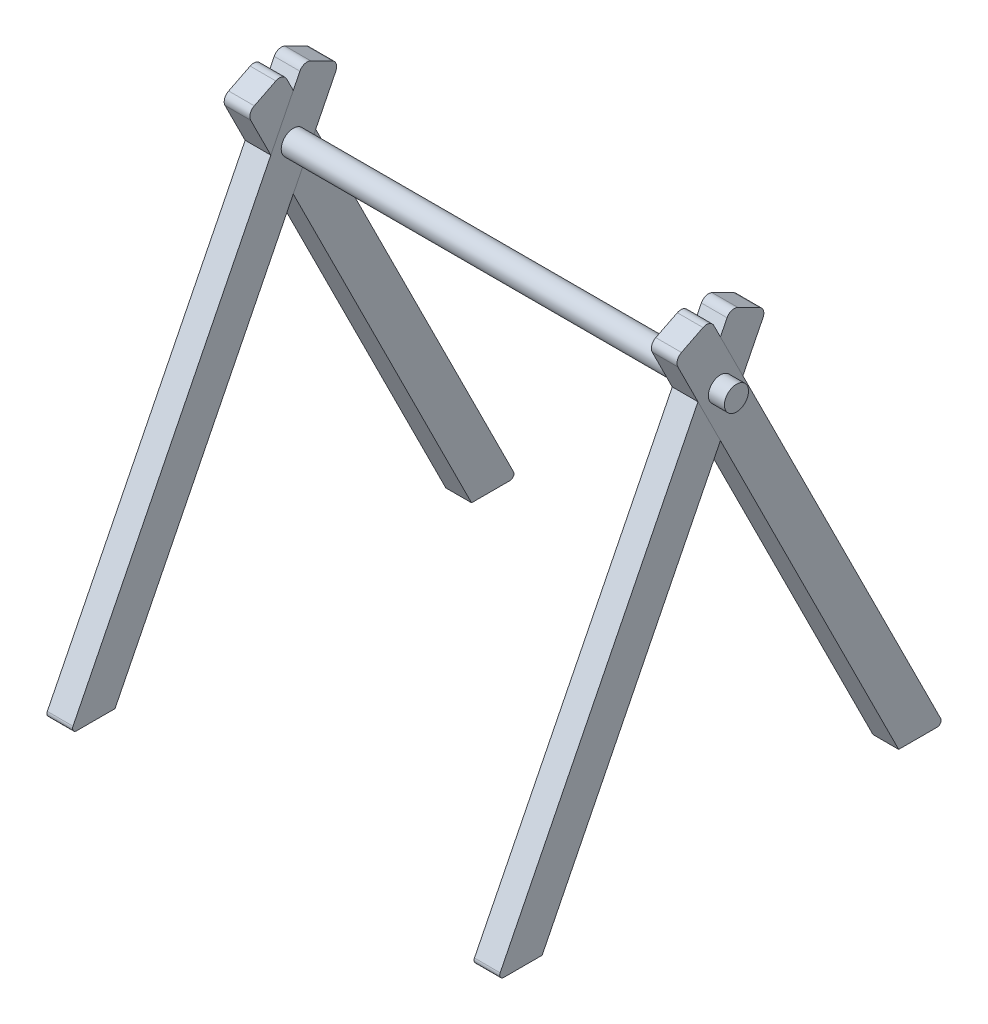
SolidWorks part; units mm, degrees
material "Pine"
ref_plane "Front Plane" through (0, 0, 0) normal (0, 0, 1) x (1, 0, 0)
ref_plane "Top Plane" through (0, 0, 0) normal (0, 1, 0) x (1, 0, 0)
ref_plane "Right Plane" through (0, 0, 0) normal (1, 0, 0) x (0, 0, -1)
sketch "Sketch1" plane through (0, 0, 0) normal (1, 0, 0) x (0, 0, -1)
  line L0 (-250, 0) -> (250, 0)
  line L1 (250, 0) -> (0, 500)
  line L2 (0, 500) -> (-250, 0)
  dimension "D1" = 500
  dimension "D2" = 500
sketch "Sketch3" plane through (0, 0, 0) normal (1, 0, 0) x (0, 0, -1)
  line L0 (-250, 0) -> (250, 0) construction
  line L1 (-402.0212, 0) -> (465.3533, 0) construction
  line L2 (12.738, 581.3777) -> (57.4593, 559.017)
  line L3 (-12.738, 581.3777) -> (-57.4593, 559.017)
  line L4 (-277.9508, 0) -> (-222.0492, 0)
  line L5 (222.0492, 0) -> (277.9508, 0)
  line L8 (-22.3607, 511.1803) -> (-272.3607, 11.1803)
  line L9 (12.738, 581.3777) -> (-277.9508, 0)
  line L10 (22.3607, 488.8197) -> (-227.6393, -11.1803)
  line L11 (57.4593, 559.017) -> (-222.0492, 0)
  line L13 (272.3607, 11.1803) -> (22.3607, 511.1803)
  line L14 (277.9508, 0) -> (-12.738, 581.3777)
  line L15 (227.6393, -11.1803) -> (-22.3607, 488.8197)
  line L16 (222.0492, 0) -> (-57.4593, 559.017)
  circle A0 centre (0, 500) radius 15
  dimension "D5" = 30
  dimension "D6" = 650
  dimension "D1" = 25
  dimension "D2" = 25
  dimension "D3" = 25
  dimension "D4" = 25
sketch "Sketch4" plane through (0, 0, 0) normal (1, 0, 0) x (0, 0, -1)
  line L0 (-277.9508, 0) -> (-222.0492, 0) construction
  line L1 (57.4593, 559.017) -> (-222.0492, 0) construction
  line L2 (12.738, 581.3777) -> (57.4593, 559.017) construction
  line L3 (12.738, 581.3777) -> (-277.9508, 0) construction
  line L4 (-277.9508, 0) -> (-222.0492, 0)
  line L5 (57.4593, 559.017) -> (-222.0492, 0)
  line L6 (12.738, 581.3777) -> (57.4593, 559.017)
  line L7 (12.738, 581.3777) -> (-277.9508, 0)
extrude "Boss-Extrude1" add sketch "Sketch4" along normal blind 32
sketch "Sketch5" plane through (0, 0, 0) normal (1, 0, 0) x (0, 0, -1)
  line L0 (-12.738, 581.3777) -> (-57.4593, 559.017) construction
  line L1 (222.0492, 0) -> (-57.4593, 559.017) construction
  line L2 (277.9508, 0) -> (-12.738, 581.3777) construction
  line L3 (222.0492, 0) -> (277.9508, 0) construction
  line L4 (222.0492, 0) -> (277.9508, 0)
  line L5 (-12.738, 581.3777) -> (-57.4593, 559.017)
  line L6 (277.9508, 0) -> (-12.738, 581.3777)
  line L7 (222.0492, 0) -> (-57.4593, 559.017)
extrude "Boss-Extrude2" add sketch "Sketch5" along normal blind 32 separate body
sketch "Sketch6" plane through (0, 0, 0) normal (-1, 0, 0) x (0, 0, 1)
  line L4 (12.738, 581.3777) -> (-277.9508, 0)
  line L5 (-277.9508, 0) -> (-222.0492, 0)
  line L6 (-222.0492, 0) -> (57.4593, 559.017)
  line L7 (57.4593, 559.017) -> (12.738, 581.3777)
  line L8 (12.738, 581.3777) -> (-277.9508, 0)
  line L9 (-277.9508, 0) -> (-222.0492, 0)
  line L10 (-222.0492, 0) -> (57.4593, 559.017)
  line L11 (57.4593, 559.017) -> (12.738, 581.3777)
  dimension "D1" = 0
extrude "Cut-Extrude1" cut sketch "Sketch6" against normal blind 16
sketch "Sketch7" plane through (32, 0, 0) normal (1, 0, 0) x (0, 0, -1)
  line L4 (12.738, 581.3777) -> (-277.9508, 0)
  line L5 (-277.9508, 0) -> (-222.0492, 0)
  line L6 (-222.0492, 0) -> (57.4593, 559.017)
  line L7 (57.4593, 559.017) -> (12.738, 581.3777)
  line L8 (12.738, 581.3777) -> (-277.9508, 0)
  line L9 (-277.9508, 0) -> (-222.0492, 0)
  line L10 (-222.0492, 0) -> (57.4593, 559.017)
  line L11 (57.4593, 559.017) -> (12.738, 581.3777)
  dimension "D1" = 0
extrude "Cut-Extrude2" cut sketch "Sketch7" against normal blind 16
sketch "Sketch8" plane through (32, 0, 0) normal (1, 0, 0) x (0, 0, -1)
  circle A0 centre (0, 500) radius 15 construction
  circle A1 centre (0, 500) radius 15
extrude "Cut-Extrude3" cut sketch "Sketch8" against normal through all
sketch "Sketch9" plane through (32, 0, 0) normal (1, 0, 0) x (0, 0, -1)
  circle A0 centre (0, 500) radius 3.25
  dimension "D1" = 6.5
extrude "Cut-Extrude4" cut sketch "Sketch9" against normal through all
fillet "Fillet1" radius 10 2 edges at (16, 559.017, 57.4593) (16, 581.3777, 12.738)
fillet "Fillet2" radius 10 2 edges at (16, 581.3777, -12.738) (16, 559.017, -57.4593)
fillet "Fillet3" radius 5 1 edges at (16, 0, 277.9508)
fillet "Fillet4" radius 5 1 edges at (16, 0, -277.9508)
ref_plane "Plane1" through (282, 0, 0) normal (1, 0, 0) x (0, 0, -1)
mirror "Mirror1" about plane through (282, 0, 0) normal (1, 0, 0) of bodies 106 107
sketch "Sketch10" plane through (16, 0, 0) normal (1, 0, 0) x (0, 0, -1)
  circle A0 centre (0, 500) radius 15 construction
  circle A1 centre (0, 500) radius 15
extrude "Boss-Extrude4" add sketch "Sketch10" along normal up to surface (532 mm away) separate body up to face at (548, 500, -3.25)
hole_wizard "M6 Tapped Hole1" positions "Sketch12" profile "Sketch14" tap size "M6" standard "ISO"
sketch "Sketch12" plane through (16, 0, 0) normal (-1, 0, 0) x (0, 0, 1)
  point P0 (0, 500)
sketch "Sketch14" plane through (16, 500, 0) normal (0, 1, 0) x (0, 0, 1)
  line L0 (0, 0) -> (0, 26.5022)
  line L1 (0, 26.5022) -> (2.5, 25)
  line L2 (2.5, 25) -> (2.5, 0)
  line L5 (2.5, 0) -> (0, 0)
  line L10 (0, 26.5022) -> (-2.5, 25) construction
  line L11 (0, -6.35) -> (0, 107.95) construction
  dimension "Tap Drill Dia." = 5
  dimension "Tap Drill Depth" = 25
  dimension "Drill Angle" = 118
cosmetic thread "Hole Thread1" parameters "D1"=22, "D2"=6
hole_wizard "M6 Tapped Hole2" positions "Sketch15" profile "Sketch16" tap size "M6" standard "ISO"
sketch "Sketch15" plane through (548, 0, 0) normal (1, 0, 0) x (0, 0, -1)
  point P0 (0, 500)
sketch "Sketch16" plane through (548, 500, 0) normal (0, 1, 0) x (0, 0, -1)
  line L0 (0, 0) -> (0, 26.5022)
  line L1 (0, 26.5022) -> (2.5, 25)
  line L2 (2.5, 25) -> (2.5, 0)
  line L5 (2.5, 0) -> (0, 0)
  line L10 (0, 26.5022) -> (-2.5, 25) construction
  line L11 (0, -6.35) -> (0, 107.95) construction
  dimension "Tap Drill Dia." = 5
  dimension "Tap Drill Depth" = 25
  dimension "Drill Angle" = 118
cosmetic thread "Hole Thread2" parameters "D1"=22, "D2"=6
sketch "Sketch17" plane through (16, 0, 0) normal (-1, 0, 0) x (0, 0, 1)
  circle A0 centre (0, 500) radius 3
  dimension "D1" = 6
extrude "Boss-Extrude5" add sketch "Sketch17" along normal blind 22 and the other way blind 20 separate body
mirror "Mirror3" about plane through (282, 0, 0) normal (1, 0, 0) of bodies 113
sketch "Sketch18" plane through (0, 0, 0) normal (-1, 0, 0) x (0, 0, 1)
  circle A1 centre (0, 500) radius 15 construction
  circle A2 centre (0, 500) radius 15
extrude "Boss-Extrude6" add sketch "Sketch18" along normal blind 20 separate body
sketch "Sketch19" plane through (0, 0, 0) normal (-1, 0, 0) x (0, 0, 1)
  circle A0 centre (0, 500) radius 3
  dimension "D1" = 6
extrude "Cut-Extrude5" cut sketch "Sketch19" along normal blind 10
mirror "Mirror4" about plane through (282, 0, 0) normal (1, 0, 0) of bodies 116
delete or keep bodies "Body-Delete/Keep 1" [suppressed] type delete bodies bodies 106 107 108 109 116 117
delete or keep bodies "Body-Delete/Keep 2" [suppressed] type delete bodies bodies 106 114 113 112 109 108 107 117
delete or keep bodies "Body-Delete/Keep 3" [suppressed] type delete bodies bodies 107 116 114 113 112 109 108 117
delete or keep bodies "Body-Delete/Keep 4" [suppressed] type delete bodies bodies 106 109 108 117 116 114 113 112
